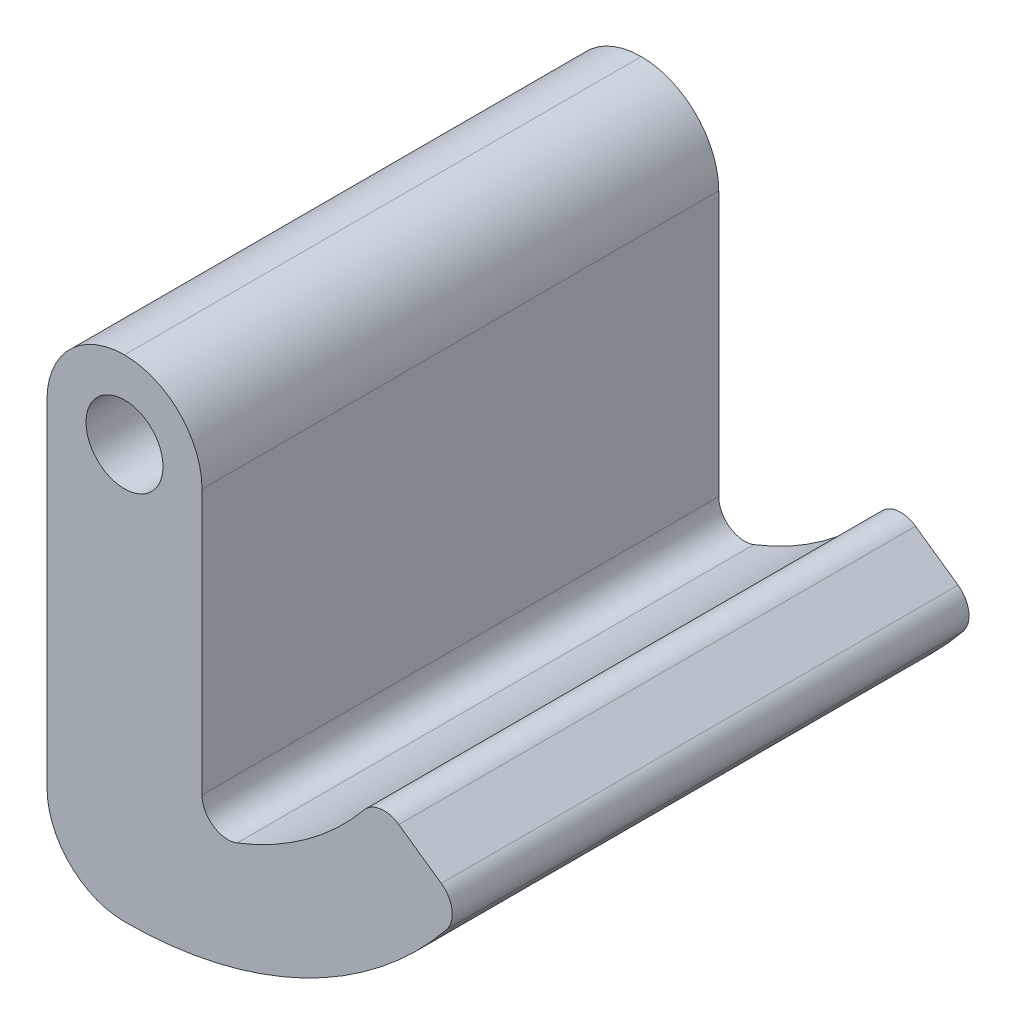
SolidWorks part; units mm, degrees
ref_plane "Front Plane" through (0, 0, 0) normal (0, 0, 1) x (1, 0, 0)
ref_plane "Top Plane" through (0, 0, 0) normal (0, 1, 0) x (1, 0, 0)
ref_plane "Right Plane" through (0, 0, 0) normal (1, 0, 0) x (0, 0, -1)
sketch "Sketch2" plane through (0, 0, 0) normal (0, 0, 1) x (1, 0, 0)
  line L1 (-6, 6) -> (6, 6)
  line L2 (-6, 6) -> (-6, -32)
  line L4 (6, 6) -> (6, -23.2379)
  line L5 (19.6596, -13.7658) -> (26.2129, -18.3544)
  line L6 (0, 0) -> (19.6596, -13.7658) construction
  line L7 (0, -24) -> (0, 0) construction
  line L10 (-6, -32) -> (0, -32)
  line L11 (0, -32) -> (0, -24) construction
  arc A0 (6, -23.2379) -> (19.6596, -13.7658) centre (0, 0) ccw
  arc A1 (0, -32) -> (26.2129, -18.3544) centre (0, 0) ccw
  circle A2 centre (0, 0) radius 2.98
  arc A3 (0, -24) -> (6, -23.2379) centre (0, 0) ccw construction
  dimension "D2" = 5.96
  dimension "D5" = 24
  dimension "D1" = 6
  dimension "D3" = 12
  dimension "D4" = 55
  dimension "D6" = 8
extrude "Boss-Extrude1" add sketch "Sketch2" along normal mid plane 40
fillet "Fillet1" radius 6 3 edges at (6, 6, 0) (-6, 6, 0) (-6, -32, 0)
fillet "Fillet2" radius 2 3 edges at (26.2129, -18.3544, 0) (19.6596, -13.7658, 0) (6, -23.2379, 0)
equation "\"D4@Sketch2\"=70-15"
